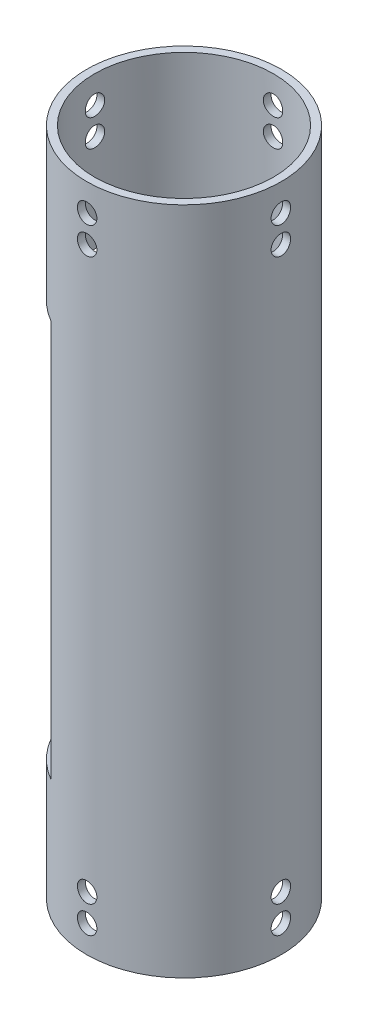
SolidWorks part; units mm, degrees
material "ПВХ 0.007 Смягченный"
ref_plane "Спереди" through (0, 0, 0) normal (0, 0, 1) x (1, 0, 0)
ref_plane "Сверху" through (0, 0, 0) normal (0, 1, 0) x (1, 0, 0)
ref_plane "Справа" through (0, 0, 0) normal (1, 0, 0) x (0, 0, -1)
sketch "Эскиз1" plane through (0, 0, 0) normal (0, 1, 0) x (1, 0, 0)
  circle A0 centre (0, 0) radius 25
  circle A1 centre (0, 0) radius 23
  dimension "ExDBody" = 50
  dimension "InDBody" = 46
extrude "Бобышка-Вытянуть1" add sketch "Эскиз1" along normal blind 172
ref_plane "Плоскость1" through (0, 31, 0) normal (0, -1, 0) x (-1, 0, 0)
sketch "Эскиз2" plane through (0, 31, 0) normal (0, -1, 0) x (-1, 0, 0)
  line L0 (0, 0) -> (29.6146, 51.294)
  line L1 (29.6146, 51.294) -> (33.4528, -57.9419)
  line L2 (33.4528, -57.9419) -> (0, 0)
  line L3 (-80.9, 0) -> (80.9, 0) construction
  dimension "D1" = 120
  dimension "D2" = 60
extrude "Вырез-Вытянуть1" cut sketch "Эскиз2" against normal blind 102
sketch "Эскиз3" plane through (0, 0, 0) normal (1, 0, 0) x (0, 0, -1)
  line L0 (23, 172) -> (-23, 172) construction
  line L1 (-25, 0) -> (25, 0) construction
  circle A0 centre (0, 165) radius 2.5
  circle A1 centre (0, 158) radius 2.5
  circle A2 centre (0, 7) radius 2.5
  circle A3 centre (0, 14) radius 2.5
  dimension "D1" = 7
  dimension "D3" = 7
  dimension "D2" = 2
  dimension "D4" = 2
extrude "Вырез-Вытянуть2" cut sketch "Эскиз3" against normal through all
pattern_circular "Круговой массив1" count 4 over 360 about axis through (0, 172, 0) along (0, -1, 0) of "Вырез-Вытянуть2"
